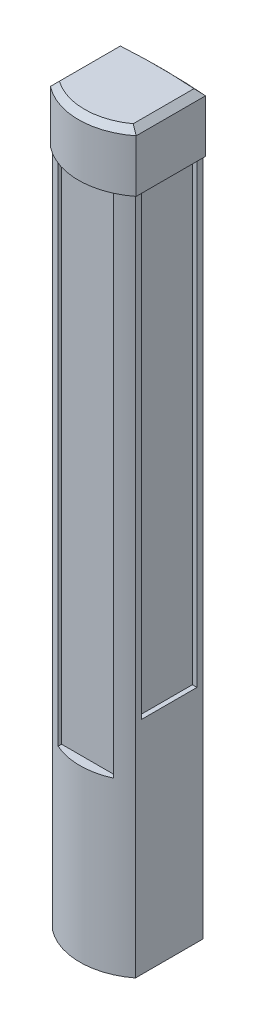
SolidWorks part; units mm, degrees
ref_plane "Ön Düzlem" through (0, 0, 0) normal (0, 0, 1) x (1, 0, 0)
ref_plane "Üst Düzlem" through (0, 0, 0) normal (0, 1, 0) x (1, 0, 0)
ref_plane "Sağ Düzlem" through (0, 0, 0) normal (1, 0, 0) x (0, 0, -1)
sketch "Çizim1" plane through (0, 0, 0) normal (0, 1, 0) x (1, 0, 0)
  line L0 (90.111, 76.6254) -> (90.111, -59.671)
  line L1 (-90.111, 75.9416) -> (-90.111, -59.671)
  line L2 (-90.111, 75.9416) -> (-90.111, 87.0912)
  line L3 (90.111, 76.6254) -> (90.111, 86.8586)
  arc A0 (-90.111, -59.671) -> (90.111, -59.671) centre (0, 57.0674) ccw
  arc A1 (-90.111, 87.0912) -> (90.111, 86.8586) centre (-1.5267, -1095.6012) cw
  dimension "D1" = 146.7622
extrude "Yükseklik-Ekstrüzyon1" add sketch "Çizim1" along normal blind 1600
sketch "Çizim2" plane through (0, 0, 0) normal (0, 0, 1) x (1, 0, 0)
  line L0 (90.111, 1600) -> (-90.111, 1600) construction
  line L1 (-60.111, 1475) -> (60.111, 1475)
  line L2 (-60.111, 1475) -> (-60.111, 370)
  line L3 (-60.111, 370) -> (60.111, 370)
  line L4 (60.111, 1475) -> (60.111, 370)
  line L5 (90.111, 1600) -> (90.111, 0) construction
  line L6 (-90.111, 1600) -> (-90.111, 0) construction
  line L7 (-90.111, 0) -> (90.111, 0) construction
  dimension "D1" = 125
  dimension "D2" = 30
  dimension "D3" = 30
  dimension "D4" = 370
extrude "Kes-Ekstrüzyon1" cut sketch "Çizim2" along normal blind 30 from offset 70 contours L1 L4 L3 L2
sketch "Çizim3" plane through (-90.111, 0, 0) normal (-1, 0, 0) x (0, 0, 1)
  line L0 (77.597, 1475) -> (90.4041, 1475) construction
  line L1 (-74.0912, 1475) -> (46.671, 1475)
  line L2 (-74.0912, 1475) -> (-74.0912, 480)
  line L3 (-74.0912, 480) -> (46.671, 480)
  line L4 (46.671, 1475) -> (46.671, 480)
  line L5 (-87.0912, 1600) -> (-87.0912, 0) construction
  line L6 (59.671, 1600) -> (59.671, 0) construction
  line L7 (90.4041, 370) -> (77.597, 370) construction
  dimension "D1" = 0
  dimension "D2" = 13
  dimension "D3" = 13
  dimension "D4" = 110
extrude "Kes-Ekstrüzyon2" cut sketch "Çizim3" against normal blind 10
mirror "Aynalama1" about plane through (0, 0, 0) normal (1, 0, 0) of "Kes-Ekstrüzyon2"
sketch "Çizim5" plane through (0, 0, 0) normal (0, 0, 1) x (1, 0, 0)
  line L0 (90.111, 1600) -> (90.111, 0) construction
  line L1 (60.111, 1475) -> (-60.111, 1475)
  line L2 (60.111, 1475) -> (60.111, 475)
  line L3 (60.111, 475) -> (-60.111, 475)
  line L4 (-60.111, 1475) -> (-60.111, 475)
  line L5 (-90.111, 1600) -> (-90.111, 0) construction
  line L6 (-60.111, 1475) -> (60.111, 1475) construction
  dimension "D1" = 30
  dimension "D2" = 0
  dimension "D3" = 30
  dimension "D4" = 1000
extrude "Kes-Ekstrüzyon3" cut sketch "Çizim5" against normal blind 20 from offset 80 offset against normal yes
sketch "Çizim6" plane through (0, 1600, 0) normal (0, 1, 0) x (1, 0, 0)
  line L0 (-93.111, 89.8717) -> (-93.111, -61.1359)
  line L1 (93.111, -61.1359) -> (93.111, 89.6318)
  line L2 (90.111, -59.671) -> (90.111, 86.8586)
  line L3 (-90.111, 87.0912) -> (-90.111, -59.671)
  line L4 (90.111, -59.671) -> (90.111, 86.8586)
  line L5 (-90.111, 87.0912) -> (-90.111, -59.671)
  arc A0 (-93.111, -61.1359) -> (93.111, -61.1359) centre (0, 57.0674) ccw
  arc A1 (93.111, 89.6318) -> (-93.111, 89.8717) centre (-1.5267, -1095.6012) ccw
  arc A2 (90.111, 86.8586) -> (-90.111, 87.0912) centre (-1.5267, -1095.6012) ccw
  arc A3 (-90.111, -59.671) -> (90.111, -59.671) centre (0, 57.0674) ccw
  arc A4 (90.111, 86.8586) -> (-90.111, 87.0912) centre (-1.5267, -1095.6012) ccw
  arc A5 (-90.111, -59.671) -> (90.111, -59.671) centre (0, 57.0674) ccw
  dimension "D1" = 0
  dimension "D2" = 3
extrude "Yükseklik-Ekstrüzyon3" add sketch "Çizim6" against normal blind 127
chamfer "Pah1" distance 13 angle 45 4 edges at (93.111, 1600, -14.248) (0.0047, 1600, -93.4031) (-93.111, 1600, -14.3679) (0, 1600, 93.4041)
